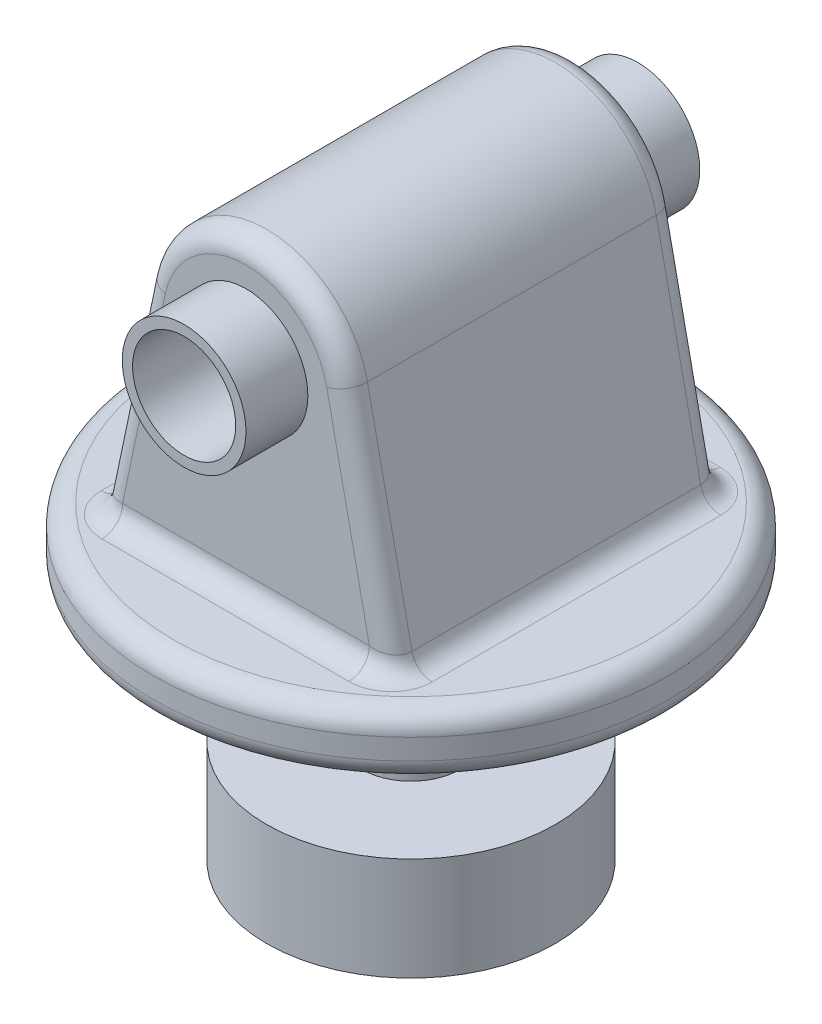
SolidWorks part; units mm, degrees
ref_plane "Front Plane" through (0, 0, 0) normal (0, 0, 1) x (1, 0, 0)
ref_plane "Top Plane" through (0, 0, 0) normal (0, 1, 0) x (1, 0, 0)
ref_plane "Right Plane" through (0, 0, 0) normal (1, 0, 0) x (0, 0, -1)
sketch "Sketch1" plane through (0, 0, 0) normal (1, 0, 0) x (0, 0, -1)
  line L0 (0, 0) -> (7, 0)
  line L1 (7, 0) -> (7, 5)
  line L2 (7, 5) -> (2.3774, 5)
  line L3 (2.3774, 5) -> (2.3774, 12)
  line L4 (2.3774, 12) -> (11.5, 12)
  line L5 (12.5, 13) -> (12.5, 14)
  line L6 (11.5, 15) -> (0, 15)
  line L7 (0, 15) -> (0, 0) construction
  line L8 (0, 0) -> (0, 15)
  arc A0 (11.5, 12) -> (12.5, 13) centre (11.5, 13) ccw
  arc A1 (12.5, 14) -> (11.5, 15) centre (11.5, 14) ccw
  point P11 (12.5, 12)
  point P14 (12.5, 15)
  dimension "D6" = 1
  dimension "D1" = 7
  dimension "D2" = 5
  dimension "D3" = 7
  dimension "D4" = 12.5
  dimension "D5" = 3
revolve "Revolve1" add sketch "Sketch1" angle 360 about L7
sketch "Sketch2" plane through (0, 0, 0) normal (0, 0, 1) x (1, 0, 0)
  line L0 (0, 15) -> (0, 25) construction
  line L1 (11.5, 15) -> (-11.5, 15) construction
  line L2 (4.8928, 26.0299) -> (7.2145, 15)
  line L3 (-4.8928, 26.0299) -> (-7.2145, 15)
  line L4 (-7.2145, 15) -> (7.2145, 15)
  arc A0 (4.8928, 26.0299) -> (-4.8928, 26.0299) centre (0, 25) ccw
  circle A1 centre (0, 25) radius 2.5
  dimension "D2" = 10
  dimension "D3" = 5
  dimension "D1" = 10
extrude "Boss-Extrude1" add sketch "Sketch2" along normal blind 8 and the other way blind 8
fillet "Fillet1" radius 1 1 edges at (6.0537, 20.515, 8) type face fillet first side face at (0, 21.5075, 8) second side face at (6.0537, 20.515, 0)
fillet "Fillet2" radius 1 1 edges at (-6.0537, 20.515, -8) type face fillet first side face at (2.5, 25, -8) second side face at (-6.0537, 20.515, -0.5)
fillet "Fillet3" radius 1 1 edges at (-7.2145, 15, 0) type face fillet first side face at (-6.0537, 20.515, 0) second side face at (0, 15, 0)
sketch "Sketch3" plane through (0, 0, 0) normal (0, -1, 0) x (1, 0, 0)
  line L0 (-6.1821, 0.3176) -> (-6.1989, 0.3268)
  line L4 (-6.1989, 0.3268) -> (-6.4775, 0.1559)
  line L5 (-6.4775, 0.1559) -> (-6.4689, -0.1709)
  line L6 (-6.4689, -0.1709) -> (-6.1816, -0.3268)
  line L7 (-5.9116, 0.1709) -> (-6.0552, 0.2488) [skipped]
  line L8 (-5.903, -0.1559) -> (-5.9073, 0.0075) [skipped]
  line L9 (-6.1816, -0.3268) -> (-6.0423, -0.2413) [skipped]
  line L10 (-6.1233, 1.0188) -> (-6.4194, 0.8802)
  line L11 (-6.4194, 0.8802) -> (-6.4474, 0.5545)
  line L12 (-6.4474, 0.5545) -> (-6.1793, 0.3674)
  line L13 (-6.1077, 1.0078) -> (-6.1233, 1.0188)
  line L14 (-5.9707, 1.6979) -> (-6.2804, 1.5934)
  line L15 (-6.2804, 1.5934) -> (-6.3447, 1.2729)
  line L16 (-6.3447, 1.2729) -> (-6.0993, 1.057)
  line L17 (-5.9564, 1.6853) -> (-5.9707, 1.6979)
  line L18 (-5.7431, 2.3558) -> (-6.0626, 2.2866)
  line L19 (-6.0626, 2.2866) -> (-6.1623, 1.9753)
  line L20 (-6.1623, 1.9753) -> (-5.9426, 1.7332)
  line L21 (-5.7303, 2.3416) -> (-5.7431, 2.3558)
  line L22 (-5.4432, 2.984) -> (-5.7684, 2.951)
  line L23 (-5.7684, 2.951) -> (-5.9024, 2.6528)
  line L24 (-5.9024, 2.6528) -> (-5.7112, 2.3877)
  line L25 (-5.4321, 2.9685) -> (-5.4432, 2.984)
  line L26 (-5.0749, 3.5747) -> (-5.4017, 3.5783)
  line L27 (-5.4017, 3.5783) -> (-5.5683, 3.297)
  line L28 (-5.5683, 3.297) -> (-5.408, 3.0121)
  line L29 (-5.0655, 3.558) -> (-5.0749, 3.5747)
  line L30 (-4.6427, 4.1204) -> (-4.9671, 4.1606)
  line L31 (-4.9671, 4.1606) -> (-5.1641, 3.8997)
  line L32 (-5.1641, 3.8997) -> (-5.0367, 3.5987)
  line L33 (-4.6353, 4.1028) -> (-4.6427, 4.1204)
  line L34 (-4.1522, 4.6143) -> (-4.4701, 4.6906)
  line L35 (-4.4701, 4.6906) -> (-4.695, 4.4534)
  line L36 (-4.695, 4.4534) -> (-4.6021, 4.14)
  line L37 (-4.1468, 4.596) -> (-4.1522, 4.6143)
  line L38 (-3.6095, 5.0502) -> (-3.9168, 5.1615)
  line L39 (-3.9168, 5.1615) -> (-4.1669, 4.9511)
  line L40 (-4.1669, 4.9511) -> (-4.1096, 4.6293)
  line L41 (-3.6061, 5.0314) -> (-3.6095, 5.0502)
  line L42 (-3.0213, 5.4226) -> (-3.3143, 5.5676)
  line L43 (-3.3143, 5.5676) -> (-3.5863, 5.3865)
  line L44 (-3.5863, 5.3865) -> (-3.5655, 5.0603)
  line L45 (-3.0201, 5.4035) -> (-3.0213, 5.4226)
  line L46 (-2.3952, 5.7268) -> (-2.67, 5.9037)
  line L47 (-2.67, 5.9037) -> (-2.9607, 5.7542)
  line L48 (-2.9607, 5.7542) -> (-2.9765, 5.4277)
  line L49 (-2.3961, 5.7077) -> (-2.3952, 5.7268)
  line L50 (-1.7389, 5.9589) -> (-1.9922, 6.1655)
  line L51 (-1.9922, 6.1655) -> (-2.2978, 6.0495)
  line L52 (-2.2978, 6.0495) -> (-2.3501, 5.7268)
  line L53 (-1.742, 5.9401) -> (-1.7389, 5.9589)
  line L54 (-1.0608, 6.1162) -> (-1.2894, 6.3498)
  line L55 (-1.2894, 6.3498) -> (-1.606, 6.2687)
  line L56 (-1.606, 6.2687) -> (-1.6941, 5.9539)
  line L57 (-1.066, 6.0978) -> (-1.0608, 6.1162)
  line L58 (-0.3694, 6.1965) -> (-0.5703, 6.4543)
  line L59 (-0.5703, 6.4543) -> (-0.8941, 6.4091)
  line L60 (-0.8941, 6.4091) -> (-1.0168, 6.1062)
  line L61 (-0.3765, 6.1788) -> (-0.3694, 6.1965)
  line L62 (0.3268, 6.1989) -> (0.1559, 6.4775)
  line L63 (0.1559, 6.4775) -> (-0.1709, 6.4689)
  line L64 (-0.1709, 6.4689) -> (-0.3268, 6.1816)
  line L65 (0.3176, 6.1821) -> (0.3268, 6.1989)
  line L66 (1.0188, 6.1233) -> (0.8802, 6.4194)
  line L67 (0.8802, 6.4194) -> (0.5545, 6.4474)
  line L68 (0.5545, 6.4474) -> (0.3674, 6.1793)
  line L69 (1.0078, 6.1077) -> (1.0188, 6.1233)
  line L70 (1.6979, 5.9707) -> (1.5934, 6.2804)
  line L71 (1.5934, 6.2804) -> (1.2729, 6.3447)
  line L72 (1.2729, 6.3447) -> (1.057, 6.0993)
  line L73 (1.6853, 5.9564) -> (1.6979, 5.9707)
  line L74 (2.3558, 5.7431) -> (2.2866, 6.0626)
  line L75 (2.2866, 6.0626) -> (1.9753, 6.1623)
  line L76 (1.9753, 6.1623) -> (1.7332, 5.9426)
  line L77 (2.3416, 5.7303) -> (2.3558, 5.7431)
  line L78 (2.984, 5.4432) -> (2.951, 5.7684)
  line L79 (2.951, 5.7684) -> (2.6528, 5.9024)
  line L80 (2.6528, 5.9024) -> (2.3877, 5.7112)
  line L81 (2.9685, 5.4321) -> (2.984, 5.4432)
  line L82 (3.5747, 5.0749) -> (3.5783, 5.4017)
  line L83 (3.5783, 5.4017) -> (3.297, 5.5683)
  line L84 (3.297, 5.5683) -> (3.0121, 5.408)
  line L85 (3.558, 5.0655) -> (3.5747, 5.0749)
  line L86 (4.1204, 4.6427) -> (4.1606, 4.9671)
  line L87 (4.1606, 4.9671) -> (3.8997, 5.1641)
  line L88 (3.8997, 5.1641) -> (3.5987, 5.0367)
  line L89 (4.1028, 4.6353) -> (4.1204, 4.6427)
  line L90 (4.6143, 4.1522) -> (4.6906, 4.4701)
  line L91 (4.6906, 4.4701) -> (4.4534, 4.695)
  line L92 (4.4534, 4.695) -> (4.14, 4.6021)
  line L93 (4.596, 4.1468) -> (4.6143, 4.1522)
  line L94 (5.0502, 3.6095) -> (5.1615, 3.9168)
  line L95 (5.1615, 3.9168) -> (4.9511, 4.1669)
  line L96 (4.9511, 4.1669) -> (4.6293, 4.1096)
  line L97 (5.0314, 3.6061) -> (5.0502, 3.6095)
  line L98 (5.4226, 3.0213) -> (5.5676, 3.3143)
  line L99 (5.5676, 3.3143) -> (5.3865, 3.5863)
  line L100 (5.3865, 3.5863) -> (5.0603, 3.5655)
  line L101 (5.4035, 3.0201) -> (5.4226, 3.0213)
  line L102 (5.7268, 2.3952) -> (5.9037, 2.67)
  line L103 (5.9037, 2.67) -> (5.7542, 2.9607)
  line L104 (5.7542, 2.9607) -> (5.4277, 2.9765)
  line L105 (5.7077, 2.3961) -> (5.7268, 2.3952)
  line L106 (5.9589, 1.7389) -> (6.1655, 1.9922)
  line L107 (6.1655, 1.9922) -> (6.0495, 2.2978)
  line L108 (6.0495, 2.2978) -> (5.7268, 2.3501)
  line L109 (5.9401, 1.742) -> (5.9589, 1.7389)
  line L110 (6.1162, 1.0608) -> (6.3498, 1.2894)
  line L111 (6.3498, 1.2894) -> (6.2687, 1.606)
  line L112 (6.2687, 1.606) -> (5.9539, 1.6941)
  line L113 (6.0978, 1.066) -> (6.1162, 1.0608)
  line L114 (6.1965, 0.3694) -> (6.4543, 0.5703)
  line L115 (6.4543, 0.5703) -> (6.4091, 0.8941)
  line L116 (6.4091, 0.8941) -> (6.1062, 1.0168)
  line L117 (6.1788, 0.3765) -> (6.1965, 0.3694)
  line L118 (6.1989, -0.3268) -> (6.4775, -0.1559)
  line L119 (6.4775, -0.1559) -> (6.4689, 0.1709)
  line L120 (6.4689, 0.1709) -> (6.1816, 0.3268)
  line L121 (6.1821, -0.3176) -> (6.1989, -0.3268)
  line L122 (6.1233, -1.0188) -> (6.4194, -0.8802)
  line L123 (6.4194, -0.8802) -> (6.4474, -0.5545)
  line L124 (6.4474, -0.5545) -> (6.1793, -0.3674)
  line L125 (6.1077, -1.0078) -> (6.1233, -1.0188)
  line L126 (5.9707, -1.6979) -> (6.2804, -1.5934)
  line L127 (6.2804, -1.5934) -> (6.3447, -1.2729)
  line L128 (6.3447, -1.2729) -> (6.0993, -1.057)
  line L129 (5.9564, -1.6853) -> (5.9707, -1.6979)
  line L130 (5.7431, -2.3558) -> (6.0626, -2.2866)
  line L131 (6.0626, -2.2866) -> (6.1623, -1.9753)
  line L132 (6.1623, -1.9753) -> (5.9426, -1.7332)
  line L133 (5.7303, -2.3416) -> (5.7431, -2.3558)
  line L134 (5.4432, -2.984) -> (5.7684, -2.951)
  line L135 (5.7684, -2.951) -> (5.9024, -2.6528)
  line L136 (5.9024, -2.6528) -> (5.7112, -2.3877)
  line L137 (5.4321, -2.9685) -> (5.4432, -2.984)
  line L138 (5.0749, -3.5747) -> (5.4017, -3.5783)
  line L139 (5.4017, -3.5783) -> (5.5683, -3.297)
  line L140 (5.5683, -3.297) -> (5.408, -3.0121)
  line L141 (5.0655, -3.558) -> (5.0749, -3.5747)
  line L142 (4.6427, -4.1204) -> (4.9671, -4.1606)
  line L143 (4.9671, -4.1606) -> (5.1641, -3.8997)
  line L144 (5.1641, -3.8997) -> (5.0367, -3.5987)
  line L145 (4.6353, -4.1028) -> (4.6427, -4.1204)
  line L146 (4.1522, -4.6143) -> (4.4701, -4.6906)
  line L147 (4.4701, -4.6906) -> (4.695, -4.4534)
  line L148 (4.695, -4.4534) -> (4.6021, -4.14)
  line L149 (4.1468, -4.596) -> (4.1522, -4.6143)
  line L150 (3.6095, -5.0502) -> (3.9168, -5.1615)
  line L151 (3.9168, -5.1615) -> (4.1669, -4.9511)
  line L152 (4.1669, -4.9511) -> (4.1096, -4.6293)
  line L153 (3.6061, -5.0314) -> (3.6095, -5.0502)
  line L154 (3.0213, -5.4226) -> (3.3143, -5.5676)
  line L155 (3.3143, -5.5676) -> (3.5863, -5.3865)
  line L156 (3.5863, -5.3865) -> (3.5655, -5.0603)
  line L157 (3.0201, -5.4035) -> (3.0213, -5.4226)
  line L158 (2.3952, -5.7268) -> (2.67, -5.9037)
  line L159 (2.67, -5.9037) -> (2.9607, -5.7542)
  line L160 (2.9607, -5.7542) -> (2.9765, -5.4277)
  line L161 (2.3961, -5.7077) -> (2.3952, -5.7268)
  line L162 (1.7389, -5.9589) -> (1.9922, -6.1655)
  line L163 (1.9922, -6.1655) -> (2.2978, -6.0495)
  line L164 (2.2978, -6.0495) -> (2.3501, -5.7268)
  line L165 (1.742, -5.9401) -> (1.7389, -5.9589)
  line L166 (1.0608, -6.1162) -> (1.2894, -6.3498)
  line L167 (1.2894, -6.3498) -> (1.606, -6.2687)
  line L168 (1.606, -6.2687) -> (1.6941, -5.9539)
  line L169 (1.066, -6.0978) -> (1.0608, -6.1162)
  line L170 (0.3694, -6.1965) -> (0.5703, -6.4543)
  line L171 (0.5703, -6.4543) -> (0.8941, -6.4091)
  line L172 (0.8941, -6.4091) -> (1.0168, -6.1062)
  line L173 (0.3765, -6.1788) -> (0.3694, -6.1965)
  line L174 (-0.3268, -6.1989) -> (-0.1559, -6.4775)
  line L175 (-0.1559, -6.4775) -> (0.1709, -6.4689)
  line L176 (0.1709, -6.4689) -> (0.3268, -6.1816)
  line L177 (-0.3176, -6.1821) -> (-0.3268, -6.1989)
  line L178 (-1.0188, -6.1233) -> (-0.8802, -6.4194)
  line L179 (-0.8802, -6.4194) -> (-0.5545, -6.4474)
  line L180 (-0.5545, -6.4474) -> (-0.3674, -6.1793)
  line L181 (-1.0078, -6.1077) -> (-1.0188, -6.1233)
  line L182 (-1.6979, -5.9707) -> (-1.5934, -6.2804)
  line L183 (-1.5934, -6.2804) -> (-1.2729, -6.3447)
  line L184 (-1.2729, -6.3447) -> (-1.057, -6.0993)
  line L185 (-1.6853, -5.9564) -> (-1.6979, -5.9707)
  line L186 (-2.3558, -5.7431) -> (-2.2866, -6.0626)
  line L187 (-2.2866, -6.0626) -> (-1.9753, -6.1623)
  line L188 (-1.9753, -6.1623) -> (-1.7332, -5.9426)
  line L189 (-2.3416, -5.7303) -> (-2.3558, -5.7431)
  line L190 (-2.984, -5.4432) -> (-2.951, -5.7684)
  line L191 (-2.951, -5.7684) -> (-2.6528, -5.9024)
  line L192 (-2.6528, -5.9024) -> (-2.3877, -5.7112)
  line L193 (-2.9685, -5.4321) -> (-2.984, -5.4432)
  line L194 (-3.5747, -5.0749) -> (-3.5783, -5.4017)
  line L195 (-3.5783, -5.4017) -> (-3.297, -5.5683)
  line L196 (-3.297, -5.5683) -> (-3.0121, -5.408)
  line L197 (-3.558, -5.0655) -> (-3.5747, -5.0749)
  line L198 (-4.1204, -4.6427) -> (-4.1606, -4.9671)
  line L199 (-4.1606, -4.9671) -> (-3.8997, -5.1641)
  line L200 (-3.8997, -5.1641) -> (-3.5987, -5.0367)
  line L201 (-4.1028, -4.6353) -> (-4.1204, -4.6427)
  line L202 (-4.6143, -4.1522) -> (-4.6906, -4.4701)
  line L203 (-4.6906, -4.4701) -> (-4.4534, -4.695)
  line L204 (-4.4534, -4.695) -> (-4.14, -4.6021)
  line L205 (-4.596, -4.1468) -> (-4.6143, -4.1522)
  line L206 (-5.0502, -3.6095) -> (-5.1615, -3.9168)
  line L207 (-5.1615, -3.9168) -> (-4.9511, -4.1669)
  line L208 (-4.9511, -4.1669) -> (-4.6293, -4.1096)
  line L209 (-5.0314, -3.6061) -> (-5.0502, -3.6095)
  line L210 (-5.4226, -3.0213) -> (-5.5676, -3.3143)
  line L211 (-5.5676, -3.3143) -> (-5.3865, -3.5863)
  line L212 (-5.3865, -3.5863) -> (-5.0603, -3.5655)
  line L213 (-5.4035, -3.0201) -> (-5.4226, -3.0213)
  line L214 (-5.7268, -2.3952) -> (-5.9037, -2.67)
  line L215 (-5.9037, -2.67) -> (-5.7542, -2.9607)
  line L216 (-5.7542, -2.9607) -> (-5.4277, -2.9765)
  line L217 (-5.7077, -2.3961) -> (-5.7268, -2.3952)
  line L218 (-5.9589, -1.7389) -> (-6.1655, -1.9922)
  line L219 (-6.1655, -1.9922) -> (-6.0495, -2.2978)
  line L220 (-6.0495, -2.2978) -> (-5.7268, -2.3501)
  line L221 (-5.9401, -1.742) -> (-5.9589, -1.7389)
  line L222 (-6.1162, -1.0608) -> (-6.3498, -1.2894)
  line L223 (-6.3498, -1.2894) -> (-6.2687, -1.606)
  line L224 (-6.2687, -1.606) -> (-5.9539, -1.6941)
  line L225 (-6.0978, -1.066) -> (-6.1162, -1.0608)
  line L226 (-6.1965, -0.3694) -> (-6.4543, -0.5703)
  line L227 (-6.4543, -0.5703) -> (-6.4091, -0.8941)
  line L228 (-6.4091, -0.8941) -> (-6.1062, -1.0168)
  line L229 (-6.1788, -0.3765) -> (-6.1965, -0.3694)
  arc A0 (-6.1816, -0.3268) -> (-6.1788, -0.3765) centre (0, 0) ccw
  arc A1 (-5.9539, -1.6941) -> (-5.9401, -1.742) centre (0, 0) ccw
  arc A2 (-5.7268, -2.3501) -> (-5.7077, -2.3961) centre (0, 0) ccw
  arc A3 (-6.1062, -1.0168) -> (-6.0978, -1.066) centre (0, 0) ccw
  arc A4 (-5.4277, -2.9765) -> (-5.4035, -3.0201) centre (0, 0) ccw
  arc A5 (-5.0603, -3.5655) -> (-5.0314, -3.6061) centre (0, 0) ccw
  arc A6 (-4.6293, -4.1096) -> (-4.596, -4.1468) centre (0, 0) ccw
  arc A7 (-4.14, -4.6021) -> (-4.1028, -4.6353) centre (0, 0) ccw
  arc A8 (-3.5987, -5.0367) -> (-3.558, -5.0655) centre (0, 0) ccw
  arc A9 (-3.0121, -5.408) -> (-2.9685, -5.4321) centre (0, 0) ccw
  arc A10 (-2.3877, -5.7112) -> (-2.3416, -5.7303) centre (0, 0) ccw
  arc A11 (-1.7332, -5.9426) -> (-1.6853, -5.9564) centre (0, 0) ccw
  arc A12 (-1.057, -6.0993) -> (-1.0078, -6.1077) centre (0, 0) ccw
  arc A13 (-0.3674, -6.1793) -> (-0.3176, -6.1821) centre (0, 0) ccw
  arc A14 (0.3268, -6.1816) -> (0.3765, -6.1788) centre (0, 0) ccw
  arc A15 (1.0168, -6.1062) -> (1.066, -6.0978) centre (0, 0) ccw
  arc A16 (1.6941, -5.9539) -> (1.742, -5.9401) centre (0, 0) ccw
  arc A17 (2.3501, -5.7268) -> (2.3961, -5.7077) centre (0, 0) ccw
  arc A18 (2.9765, -5.4277) -> (3.0201, -5.4035) centre (0, 0) ccw
  arc A19 (3.5655, -5.0603) -> (3.6061, -5.0314) centre (0, 0) ccw
  arc A20 (4.1096, -4.6293) -> (4.1468, -4.596) centre (0, 0) ccw
  arc A21 (4.6021, -4.14) -> (4.6353, -4.1028) centre (0, 0) ccw
  arc A22 (5.0367, -3.5987) -> (5.0655, -3.558) centre (0, 0) ccw
  arc A23 (5.408, -3.0121) -> (5.4321, -2.9685) centre (0, 0) ccw
  arc A24 (5.7112, -2.3877) -> (5.7303, -2.3416) centre (0, 0) ccw
  arc A25 (5.9426, -1.7332) -> (5.9564, -1.6853) centre (0, 0) ccw
  arc A26 (6.0993, -1.057) -> (6.1077, -1.0078) centre (0, 0) ccw
  arc A27 (6.1793, -0.3674) -> (6.1821, -0.3176) centre (0, 0) ccw
  arc A28 (6.1816, 0.3268) -> (6.1788, 0.3765) centre (0, 0) ccw
  arc A29 (6.1062, 1.0168) -> (6.0978, 1.066) centre (0, 0) ccw
  arc A30 (5.9539, 1.6941) -> (5.9401, 1.742) centre (0, 0) ccw
  arc A31 (5.7268, 2.3501) -> (5.7077, 2.3961) centre (0, 0) ccw
  arc A32 (5.4277, 2.9765) -> (5.4035, 3.0201) centre (0, 0) ccw
  arc A33 (5.0603, 3.5655) -> (5.0314, 3.6061) centre (0, 0) ccw
  arc A34 (4.6293, 4.1096) -> (4.596, 4.1468) centre (0, 0) ccw
  arc A35 (4.14, 4.6021) -> (4.1028, 4.6353) centre (0, 0) ccw
  arc A36 (3.5987, 5.0367) -> (3.558, 5.0655) centre (0, 0) ccw
  arc A37 (3.0121, 5.408) -> (2.9685, 5.4321) centre (0, 0) ccw
  arc A38 (2.3877, 5.7112) -> (2.3416, 5.7303) centre (0, 0) ccw
  arc A39 (1.7332, 5.9426) -> (1.6853, 5.9564) centre (0, 0) ccw
  arc A40 (1.057, 6.0993) -> (1.0078, 6.1077) centre (0, 0) ccw
  arc A41 (0.3674, 6.1793) -> (0.3176, 6.1821) centre (0, 0) ccw
  arc A42 (-0.3268, 6.1816) -> (-0.3765, 6.1788) centre (0, 0) ccw
  arc A43 (-1.0168, 6.1062) -> (-1.066, 6.0978) centre (0, 0) ccw
  arc A44 (-1.6941, 5.9539) -> (-1.742, 5.9401) centre (0, 0) ccw
  arc A45 (-2.3501, 5.7268) -> (-2.3961, 5.7077) centre (0, 0) ccw
  arc A46 (-2.9765, 5.4277) -> (-3.0201, 5.4035) centre (0, 0) ccw
  arc A47 (-3.5655, 5.0603) -> (-3.6061, 5.0314) centre (0, 0) ccw
  arc A48 (-4.6021, 4.14) -> (-4.6353, 4.1028) centre (0, 0) ccw
  arc A49 (-4.1096, 4.6293) -> (-4.1468, 4.596) centre (0, 0) ccw
  arc A50 (-5.0367, 3.5987) -> (-5.0655, 3.558) centre (0, 0) ccw
  arc A51 (-5.408, 3.0121) -> (-5.4321, 2.9685) centre (0, 0) ccw
  arc A52 (-5.7112, 2.3877) -> (-5.7303, 2.3416) centre (0, 0) ccw
  arc A53 (-6.1793, 0.3674) -> (-6.1821, 0.3176) centre (0, 0) ccw
  arc A54 (-6.0993, 1.057) -> (-6.1077, 1.0078) centre (0, 0) ccw
  arc A55 (-5.9426, 1.7332) -> (-5.9564, 1.6853) centre (0, 0) ccw
  point P292 (0, 0)
  dimension "D1" = 56
extrude "Cut-Extrude1" cut sketch "Sketch3" against normal blind 2.5
sketch "Sketch4" plane through (0, 2.5, 0) normal (0, -1, 0) x (1, 0, 0)
  circle A0 centre (0, 0) radius 3
  dimension "D1" = 6
extrude "Cut-Extrude2" cut sketch "Sketch4" against normal blind 1.5
sketch "Sketch6" plane through (0, 0, -8) normal (0, 0, -1) x (-1, 0, 0)
  circle A0 centre (0, 25) radius 2.5
  circle A1 centre (0, 25) radius 3
  dimension "D1" = 0.5
extrude "Boss-Extrude2" add sketch "Sketch6" along normal blind 3
sketch "Sketch7" plane through (0, 0, 8) normal (0, 0, 1) x (1, 0, 0)
  circle A0 centre (0, 25) radius 2.5
  circle A1 centre (0, 25) radius 3
  dimension "D1" = 0.5
extrude "Boss-Extrude3" add sketch "Sketch7" along normal blind 3
